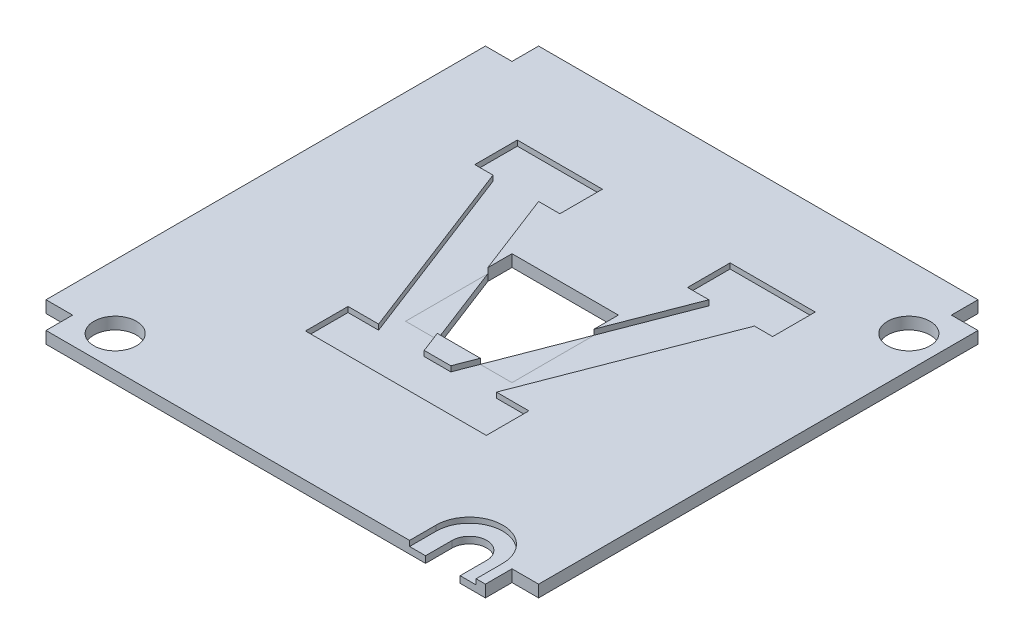
SolidWorks part; units mm, degrees
ref_plane "Front" through (0, 0, 0) normal (0, 0, 1) x (1, 0, 0)
ref_plane "Top" through (0, 0, 0) normal (0, 1, 0) x (1, 0, 0)
ref_plane "Right" through (0, 0, 0) normal (1, 0, 0) x (0, 0, -1)
sketch "Sketch2" plane through (0, 0, 0) normal (0, 1, 0) x (1, 0, 0)
  line L1 (-46.3, 41.3) -> (46.3, 41.3)
  line L2 (-46.3, 41.3) -> (-46.3, -41.3)
  line L3 (-46.3, -41.3) -> (46.3, -41.3)
  line L4 (46.3, 41.3) -> (46.3, -41.3)
  line L5 (-46.3, 41.3) -> (46.3, -41.3) construction
  line L6 (-46.3, -41.3) -> (46.3, 41.3) construction
  line L7 (-41.3, 46.3) -> (41.3, 46.3)
  line L8 (-41.3, 46.3) -> (-41.3, -46.3)
  line L9 (-41.3, -46.3) -> (41.3, -46.3)
  line L10 (41.3, 46.3) -> (41.3, -46.3)
  line L11 (-41.3, 46.3) -> (41.3, -46.3) construction
  line L12 (-41.3, -46.3) -> (41.3, 46.3) construction
  point P0 (0, 0)
  point P6 (0, 0)
  dimension "D1" = 82.6
  dimension "D2" = 92.6
  dimension "D3" = 92.6
  dimension "D4" = 82.6
extrude "Boss-Extrude1" add sketch "Sketch2" along normal blind 2.25 contours L8 L1 L2 L3 | L10 L1 L8 L3 | L10 L3 L8 L9 | L1 L10 L3 L4 | L10 L7 L8 L1 region at (-43.8, 0, 0) region at (0, 0, -43.8) region at (0, 0, 0) region at (43.8, 0, 0) region at (0, 0, 43.8)
sketch "Sketch3" plane through (0, 2.25, 0) normal (0, 1, 0) x (1, 0, 0)
  line L0 (-41.3, 46.3) -> (41.3, 46.3) construction
  line L1 (-46.3, 41.3) -> (-46.3, -41.3) construction
  line L2 (46.3, 41.3) -> (46.3, -41.3) construction
  line L3 (-41.3, -46.3) -> (41.3, -46.3) construction
  circle A0 centre (-34.3, -40.3) radius 4
  circle A1 centre (40.3, 34.3) radius 4
  dimension "D1" = 8
  dimension "D2" = 8
  dimension "D3" = 6
  dimension "D4" = 12
  dimension "D5" = 12
  dimension "D6" = 6
extrude "Cut-Extrude1" cut sketch "Sketch3" against normal blind 10
sketch "Sketch4" plane through (0, 2.25, 0) normal (0, 1, 0) x (1, 0, 0)
  line L1 (-38.2288, 21.7712) -> (-18.2288, 21.7712)
  line L2 (-38.2288, 21.7712) -> (-38.2288, -8.2288)
  line L3 (-38.2288, -8.2288) -> (-18.2288, -8.2288)
  line L4 (-18.2288, 21.7712) -> (-18.2288, -8.2288)
  line L5 (-8.2288, 38.2288) -> (21.7712, 38.2288)
  line L6 (-8.2288, 38.2288) -> (-8.2288, 18.2288)
  line L7 (-8.2288, 18.2288) -> (21.7712, 18.2288)
  line L8 (21.7712, 38.2288) -> (21.7712, 18.2288)
  line L9 (38.2288, -21.7712) -> (18.2288, -21.7712)
  line L10 (38.2288, -21.7712) -> (38.2288, 8.2288)
  line L11 (38.2288, 8.2288) -> (18.2288, 8.2288)
  line L12 (18.2288, -21.7712) -> (18.2288, 8.2288)
  line L13 (8.2288, -18.2288) -> (-21.7712, -18.2288)
  line L14 (8.2288, -18.2288) -> (8.2288, -38.2288)
  line L15 (8.2288, -38.2288) -> (-21.7712, -38.2288)
  line L16 (-21.7712, -18.2288) -> (-21.7712, -38.2288)
  circle A0 centre (0, 0) radius 20 construction
  dimension "D11" = 40
  dimension "D1" = 20
  dimension "D2" = 30
  dimension "D3" = 10
  dimension "D4" = 30
  dimension "D5" = 20
  dimension "D6" = 30
  dimension "D7" = 20
  dimension "D8" = 30
  dimension "D9" = 20
  dimension "D10" = 10
  dimension "D12" = 10
  dimension "D13" = 10
extrude "Cut-Extrude2" [suppressed] cut sketch "Sketch4" against normal blind 10
sketch "Sketch5" plane through (0, 2.25, 0) normal (0, 1, 0) x (1, 0, 0)
  line L0 (30.05, -41.3) -> (30.05, -46.3)
  line L1 (-41.3, -46.3) -> (41.3, -46.3) construction
  line L2 (30.05, -46.3) -> (36.55, -46.3)
  line L3 (36.55, -46.3) -> (36.55, -41.3)
  line L4 (46.3, 41.3) -> (46.3, -41.3) construction
  arc A0 (30.05, -41.3) -> (36.55, -41.3) centre (33.3, -41.3) cw
  dimension "D1" = 5
  dimension "D2" = 3.25
  dimension "D3" = 13
extrude "Cut-Extrude3" cut sketch "Sketch5" against normal blind 10
sketch "Sketch6" plane through (0, 2.25, 0) normal (0, 1, 0) x (1, 0, 0)
  line L0 (27.05, -46.3) -> (27.05, -41.3)
  line L1 (-41.3, -46.3) -> (30.05, -46.3) construction
  line L2 (39.55, -46.3) -> (39.55, -41.3)
  line L4 (27.05, -41.3) -> (30.05, -41.3) construction
  line L5 (36.55, -46.3) -> (41.3, -46.3) construction
  line L8 (36.55, -46.3) -> (36.55, -41.3) construction
  line L9 (39.55, -41.3) -> (36.55, -41.3) construction
  line L10 (27.05, -46.3) -> (30.05, -46.3)
  line L11 (30.05, -46.3) -> (30.05, -41.3)
  line L12 (30.05, -41.3) -> (36.55, -41.3)
  line L13 (36.55, -41.3) -> (36.55, -46.3)
  line L14 (36.55, -46.3) -> (39.55, -46.3)
  arc A0 (27.05, -41.3) -> (39.55, -41.3) centre (33.3, -41.3) cw
  point P13 (39.55, -43.8)
  dimension "D3" = 6.25
  dimension "D1" = 3
  dimension "D2" = 3
extrude "Cut-Extrude4" cut sketch "Sketch6" against normal blind 1
sketch "Sketch7" plane through (0, 2.25, 0) normal (0, 1, 0) x (1, 0, 0)
  line L1 (-10, 10) -> (10, 10)
  line L2 (-10, 10) -> (-10, -10)
  line L3 (-10, -10) -> (10, -10)
  line L4 (10, 10) -> (10, -10)
  line L5 (-10, 10) -> (10, -10) construction
  line L6 (-10, -10) -> (10, 10) construction
  point P0 (0, 0)
  dimension "D1" = 20
  dimension "D2" = 20
extrude "Cut-Extrude5" cut sketch "Sketch7" against normal blind 10
sketch "Sketch9" [suppressed] plane through (0, 2.25, 0) normal (0, 1, 0) x (1, 0, 0)
  line L0 (-38.2288, -8.2288) -> (-18.2288, -8.2288) construction
  line L1 (-38.2288, 21.7712) -> (-31.2481, 21.7712)
  line L2 (-38.2288, 21.7712) -> (-38.2288, -8.2288)
  line L3 (-38.2288, -8.2288) -> (-31.2481, -8.2288)
  line L4 (-31.2481, 21.7712) -> (-31.2481, -8.2288)
extrude "Boss-Extrude2" [suppressed] add sketch "Sketch9" against normal blind 2.25
sketch "Sketch18" plane through (0, 2.25, 0) normal (0, 1, 0) x (1, 0, 0)
  line L0 (-24.5745, 21) -> (-11.0745, -14)
  line L1 (-28, 29) -> (-12, 29)
  line L2 (-28, 29) -> (-28, 21)
  line L3 (-28, 21) -> (-12, 21)
  line L4 (-12, 29) -> (-12, 21)
  line L5 (12, 29) -> (28, 29)
  line L6 (12, 29) -> (12, 21)
  line L7 (12, 21) -> (28, 21)
  line L8 (28, 29) -> (28, 21)
  line L9 (-16.8241, -14) -> (17.1759, -14)
  line L10 (-16.8241, -14) -> (-16.8241, -22)
  line L11 (-16.8241, -22) -> (17.1759, -22)
  line L12 (17.1759, -14) -> (17.1759, -22)
  line L13 (-11.0745, -14) -> (-2.5, -14)
  line L14 (-2.5, -14) -> (-16, 21)
  line L15 (2.5, -14) -> (16, 21)
  line L16 (24.5745, 21) -> (11.0745, -14)
  line L17 (0, 0) -> (0, -14) construction
  line L18 (-24.5745, 21) -> (-16, 21) construction
  line L19 (-10, -10) -> (10, -10) construction
  line L20 (16, 21) -> (24.5745, 21) construction
  point P25 (20, 21)
  dimension "D1" = 8
  dimension "D2" = 8
  dimension "D3" = 2.5
  dimension "D4" = 2.5
  dimension "D5" = 34
  dimension "D6" = 8
  dimension "D7" = 8
  dimension "D8" = 8
  dimension "D9" = 16
  dimension "D10" = 16
  dimension "D11" = 35
  dimension "D12" = 4
  dimension "D13" = 12
  dimension "D14" = 12
  dimension "D15" = 4
  dimension "D16" = 4
extrude "Cut-Extrude7" cut sketch "Sketch18" against normal blind 1 contours L9 L14 L3 L0 | L16 L7 L15 L9 | L4 L1 L2 L3 | L8 L5 L6 L7 | L12 L9 L10 L11 region at (-13.5372, 2.25, -3.5) region at (-20, 2.25, -25) region at (0.1759, 2.25, 18) region at (13.5372, 2.25, -3.5) region at (20, 2.25, -25)
sketch "Sketch19" plane through (0, 2.25, 0) normal (0, 1, 0) x (1, 0, 0)
  line L0 (-10, 5.4444) -> (-4.0429, -10)
  line L1 (-4.0429, -10) -> (4.0429, -10) construction
  line L2 (-2.5, -14) -> (-4.0429, -10) construction
  line L4 (4.0429, -10) -> (10, 5.4444)
  line L5 (10, 5.4444) -> (10, -10)
  line L6 (10, 5.4444) -> (10, -10) construction
  line L7 (10, -10) -> (4.0429, -10) construction
  line L8 (10, -10) -> (-10, -10)
  line L9 (-10, -10) -> (-10, 5.4444)
extrude "Boss-Extrude3" add sketch "Sketch19" against normal blind 2.25 separate body contours L9 L8 L0 | L8 L5 L4 region at (8.0143, 2.25, 4.8519) region at (-8.0143, 2.25, 4.8519)
sketch "Sketch20" plane through (0, 2.25, 0) normal (0, 1, 0) x (1, 0, 0)
  line L0 (-10, 5.4444) -> (-10, -10)
  line L1 (-10, -10) -> (-4.0429, -10)
  line L2 (-4.0429, -10) -> (-10, 5.4444)
  line L3 (4.0429, -10) -> (10, 5.4444)
  line L4 (10, 5.4444) -> (10, -10)
  line L5 (10, -10) -> (4.0429, -10)
extrude "Cut-Extrude8" cut sketch "Sketch20" against normal blind 1
